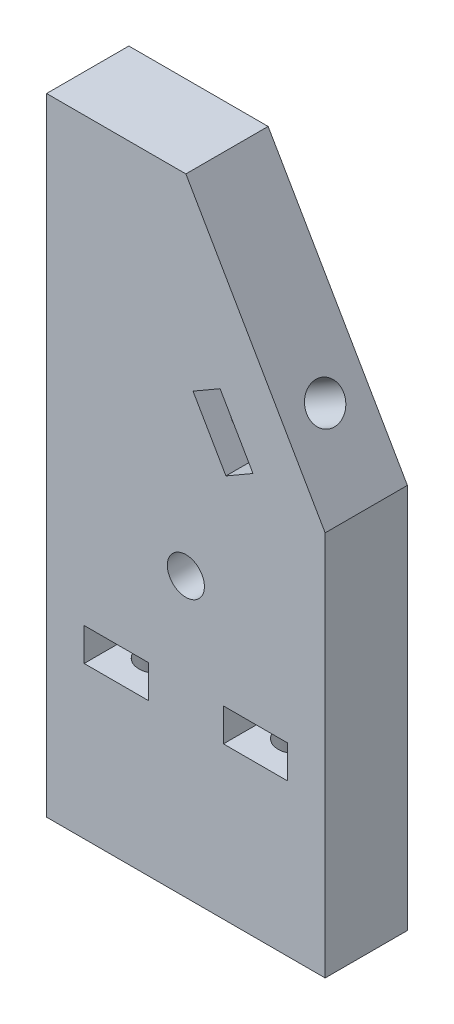
SolidWorks part; units mm, degrees
ref_plane "Front Plane" through (0, 0, 0) normal (0, 0, 1) x (1, 0, 0)
ref_plane "Top Plane" through (0, 0, 0) normal (0, 1, 0) x (1, 0, 0)
ref_plane "Right Plane" through (0, 0, 0) normal (1, 0, 0) x (0, 0, -1)
sketch "Sketch1" plane through (0, 0, 0) normal (0, 0, 1) x (1, 0, 0)
  line L0 (0, -28.803) -> (0, 28.803)
  line L1 (0, 28.803) -> (-25.4, 72.797)
  line L2 (-25.4, 72.797) -> (-25.4, -28.803) construction
  line L3 (-25.4, -28.803) -> (0, -28.803)
  line L4 (-25.4, 72.797) -> (-50.8, 72.797)
  line L5 (-50.8, 72.797) -> (-50.8, -28.803)
  line L6 (-50.8, -28.803) -> (-25.4, -28.803)
  point P4 (0, 0)
  dimension "D1" = 30
  dimension "D2" = 50.8
  dimension "D3" = 101.6
  dimension "D4" = 50.8
extrude "Boss-Extrude1" add sketch "Sketch1" along normal mid plane 15
sketch "Sketch2" plane through (12.472, 7.2007, 0) normal (0.866, 0.5, 0) x (0, 0, -1)
  line L0 (0, 24.9441) -> (0, 75.7441) construction
  line L1 (-7.5, 24.9441) -> (7.5, 24.9441) construction
  line L2 (3.4641, 33.9441) -> (7.5, 33.9441)
  line L3 (-7.5, 75.7441) -> (7.5, 75.7441) construction
  line L4 (6.9282, 39.9441) -> (3.4641, 45.9441) construction
  line L5 (3.4641, 45.9441) -> (-3.4641, 45.9441)
  line L6 (-3.4641, 45.9441) -> (-6.9282, 39.9441) construction
  line L7 (-6.9282, 39.9441) -> (-3.4641, 33.9441) construction
  line L8 (-3.4641, 33.9441) -> (3.4641, 33.9441)
  line L9 (3.4641, 33.9441) -> (6.9282, 39.9441) construction
  line L10 (7.5, 24.9441) -> (7.5, 75.7441) construction
  line L13 (7.5, 33.9441) -> (7.5, 45.9441)
  line L14 (7.5, 45.9441) -> (3.4641, 45.9441)
  line L15 (-3.4641, 45.9441) -> (-7.5, 45.9441)
  line L16 (-7.5, 24.9441) -> (-7.5, 75.7441) construction
  line L17 (-7.5, 45.9441) -> (-7.5, 33.9441)
  line L18 (-7.5, 33.9441) -> (-3.4641, 33.9441)
  line L19 (0, 39.9441) -> (6.9282, 39.9441) construction
  circle A0 centre (0, 39.9441) radius 6 construction
  dimension "D1" = 12
  dimension "D2" = 15
extrude "Cut-Extrude1" cut sketch "Sketch2" against normal blind 5.7 from offset 10 offset against normal yes
hole_wizard "17/64 (0.26563) Diameter Hole1" positions "Sketch4" profile "Sketch5" hole size "17/64" standard "ANSI Inch" end condition through all
sketch "Sketch4" plane through (3.8118, 2.2007, 0) normal (-0.866, -0.5, 0) x (0, 0, 1)
  line L3 (7.5, 33.9441) -> (-7.5, 45.9441) construction
  point P0 (0, 39.9441)
sketch "Sketch5" plane through (-16.1603, 36.7933, 0) normal (0, 0, 1) x (0.5, -0.866, 0)
  line L0 (0, 0) -> (0, 31.997)
  line L1 (0, 31.997) -> (3.3735, 31.997)
  line L2 (3.3735, 31.997) -> (3.3735, 0)
  line L5 (3.3735, 0) -> (0, 0)
  line L11 (0, -6.35) -> (0, 107.95) construction
  dimension "Thru Hole Dia." = 6.747
  dimension "Thru Hole Depth" = 31.997
sketch "Sketch6" plane through (0, -28.803, 0) normal (0, -1, 0) x (1, 0, 0)
  line L0 (-50.8, 0) -> (0, 0) construction
  line L1 (-50.8, 7.5) -> (-50.8, -7.5) construction
  line L2 (0, 7.5) -> (0, -7.5) construction
  line L3 (-38.1, 0) -> (-38.1, 6.755) construction
  line L4 (-38.1, 6.755) -> (-43.95, 3.3775) construction
  line L5 (-43.95, 3.3775) -> (-43.95, -3.3775)
  line L6 (-43.95, -3.3775) -> (-38.1, -6.755) construction
  line L7 (-38.1, -6.755) -> (-32.25, -3.3775) construction
  line L8 (-32.25, -3.3775) -> (-32.25, 3.3775)
  line L9 (-32.25, 3.3775) -> (-38.1, 6.755) construction
  line L10 (-18.55, 3.3775) -> (-18.55, -3.3775)
  line L11 (-18.55, -3.3775) -> (-12.7, -6.755) construction
  line L12 (-12.7, -6.755) -> (-6.85, -3.3775) construction
  line L13 (-6.85, -3.3775) -> (-6.85, 3.3775)
  line L14 (-6.85, 3.3775) -> (-12.7, 6.755) construction
  line L15 (-12.7, 6.755) -> (-18.55, 3.3775) construction
  line L16 (-12.7, 0) -> (-12.7, 6.755) construction
  line L17 (-18.55, -3.3775) -> (-18.55, -7.5)
  line L18 (-50.8, -7.5) -> (0, -7.5) construction
  line L19 (-18.55, -7.5) -> (-6.85, -7.5)
  line L20 (-6.85, -7.5) -> (-6.85, -3.3775)
  line L21 (-6.85, 3.3775) -> (-6.85, 7.5)
  line L22 (-50.8, 7.5) -> (0, 7.5) construction
  line L23 (-6.85, 7.5) -> (-18.55, 7.5)
  line L24 (-18.55, 7.5) -> (-18.55, 3.3775)
  line L25 (-32.25, -3.3775) -> (-32.25, -7.5)
  line L26 (-32.25, -7.5) -> (-43.95, -7.5)
  line L27 (-43.95, -7.5) -> (-43.95, -3.3775)
  line L28 (-43.95, 3.3775) -> (-43.95, 7.5)
  line L29 (-43.95, 7.5) -> (-32.25, 7.5)
  line L30 (-32.25, 7.5) -> (-32.25, 3.3775)
  circle A0 centre (-38.1, 0) radius 5.85 construction
  circle A1 centre (-12.7, 0) radius 5.85 construction
  dimension "D1" = 11.7
  dimension "D2" = 12.7
  dimension "D3" = 12.7
extrude "Cut-Extrude2" cut sketch "Sketch6" against normal blind 6 from offset 15 offset against normal yes
hole_wizard "17/64 (0.26563) Diameter Hole2" positions "Sketch7" profile "Sketch8" hole size "17/64" standard "ANSI Inch" end condition through all
sketch "Sketch7" plane through (0, -13.803, 0) normal (0, 1, 0) x (1, 0, 0)
  line L2 (-32.25, -7.5) -> (-43.95, 7.5) construction
  line L4 (-18.55, 7.5) -> (-6.85, -7.5) construction
  point P7 (-38.1, 0)
  point P16 (-12.7, 0)
sketch "Sketch8" plane through (-38.1, -13.803, 0) normal (1, 0, 0) x (0, 0, 1)
  line L0 (0, 0) -> (0, 15)
  line L1 (0, 15) -> (3.3735, 15)
  line L2 (3.3735, 15) -> (3.3735, 0)
  line L5 (3.3735, 0) -> (0, 0)
  line L11 (0, -6.35) -> (0, 107.95) construction
  dimension "Thru Hole Dia." = 6.747
  dimension "Thru Hole Depth" = 15
sketch "Sketch10" plane through (0, -28.803, 0) normal (0, -1, 0) x (1, 0, 0)
  circle A0 centre (-38.1, 0) radius 3.3735
  circle A1 centre (-12.7, 0) radius 3.3735
  circle A2 centre (-12.7, 0) radius 3.3735 construction
  circle A3 centre (-38.1, 0) radius 3.3735 construction
extrude "Cut-Extrude4" cut sketch "Sketch10" against normal offset from surface (31 mm away) 10 up to face at (-38.1, -7.803, 0) offset beyond the face yes
sketch "Sketch11" plane through (12.472, 7.2007, 0) normal (0.866, 0.5, 0) x (0, 0, -1)
  circle A0 centre (0, 39.9441) radius 3.3735
  circle A1 centre (0, 39.9441) radius 3.3735 construction
extrude "Cut-Extrude5" cut sketch "Sketch11" against normal offset from surface (25.7 mm away) 10 up to face at (-21.0966, 33.9433, 0) offset beyond the face yes
hole_wizard "1/4 Clearance Hole1" positions "Sketch12" profile "Sketch13" hole size "1/4" standard "ANSI Inch" end condition through all
sketch "Sketch12" plane through (0, 0, 7.5) normal (0, 0, 1) x (1, 0, 0)
  line L0 (-25.4, 9.297) -> (-25.4, -28.803) construction
  line L1 (-50.8, -28.803) -> (0, -28.803) construction
  line L3 (-25.4, 9.297) -> (-50.8, 9.297) construction
  line L4 (-50.8, 72.797) -> (-50.8, -28.803) construction
  point P0 (-25.4, 9.297)
  dimension "D1" = 38.1
sketch "Sketch13" plane through (-25.4, 9.297, 7.5) normal (1, 0, 0) x (0, -1, 0)
  line L0 (0, 0) -> (0, 15)
  line L1 (0, 15) -> (3.3782, 15)
  line L2 (3.3782, 15) -> (3.3782, 0)
  line L5 (3.3782, 0) -> (0, 0)
  line L11 (0, -6.35) -> (0, 107.95) construction
  dimension "Thru Hole Dia." = 6.7564
  dimension "Thru Hole Depth" = 15
other "Move Face1" face at (-38.1, -28.803, 3.3735) offset 12.7 parameters "D1"=12.7
